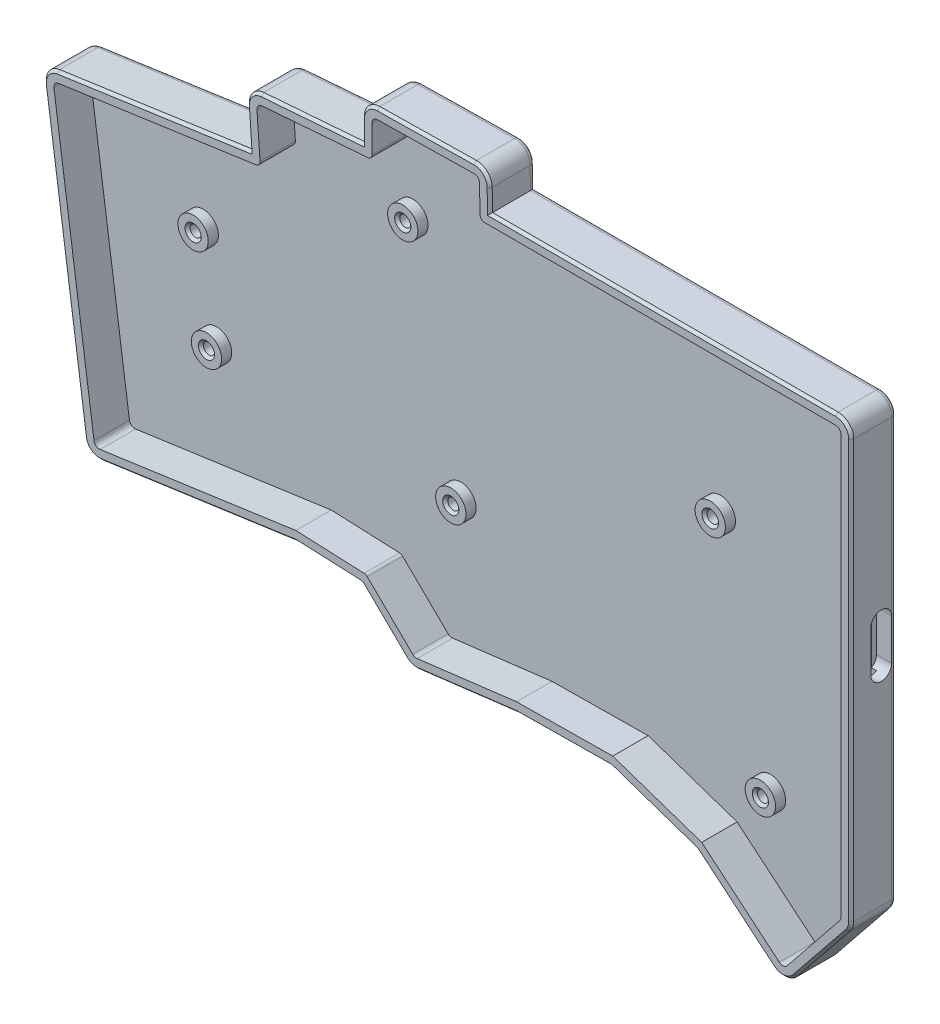
SolidWorks part; units mm, degrees
ref_plane "Front Plane" through (0, 0, 0) normal (0, 0, 1) x (1, 0, 0)
ref_plane "Top Plane" through (0, 0, 0) normal (0, 1, 0) x (1, 0, 0)
ref_plane "Right Plane" through (0, 0, 0) normal (1, 0, 0) x (0, 0, -1)
sketch "Sketch3" plane through (0, 0, 0) normal (0, 0, 1) x (1, 0, 0)
  line L0 (85.1833, 97.7805) -> (154.5968, 97.7805)
  line L1 (155.6718, 96.7055) -> (155.6718, 14.0578)
  line L2 (155.4344, 13.384) -> (144.9894, 0.4011)
  line L3 (143.4619, 0.2505) -> (128.1082, 13.0973)
  line L4 (128.1082, 13.0973) -> (143.4619, 0.2505)
  line L5 (128.1082, 13.0973) -> (110.5249, 19.0829)
  line L6 (110.5249, 19.0829) -> (91.5019, 18.8692)
  line L7 (91.5019, 18.8692) -> (71.8411, 16.4484)
  line L8 (70.9583, 16.7466) -> (61.9589, 25.5411)
  line L9 (70.9583, 16.7466) -> (61.9589, 25.5411)
  line L10 (61.3523, 25.8037) -> (47.8521, 26.3837)
  line L11 (47.8521, 26.3837) -> (9.158, 20.9127)
  line L12 (7.9428, 21.8276) -> (0.0098, 78.274)
  line L13 (0.9224, 79.4879) -> (39.9728, 85.0637)
  line L14 (40.7648, 86.0439) -> (40.1665, 94.5997)
  line L15 (41.1563, 95.7465) -> (62.0679, 97.3591)
  line L16 (62.9218, 98.2813) -> (62.9218, 103.7219)
  line L17 (63.979, 104.7967) -> (83.0927, 105.1138)
  line L18 (84.1855, 104.0536) -> (84.2584, 98.6929)
  line L19 (61.2805, 24.8059) -> (47.901, 25.3807)
  line L20 (47.901, 25.3807) -> (9.298, 19.9225)
  line L21 (6.9525, 21.6885) -> (-0.9804, 78.1349)
  line L22 (0.7811, 80.4778) -> (39.7624, 86.0438)
  line L23 (39.7624, 86.0438) -> (39.169, 94.5299)
  line L24 (41.0794, 96.7436) -> (61.9218, 98.3508)
  line L25 (61.9218, 98.3508) -> (61.9218, 103.7219)
  line L26 (63.9624, 105.7966) -> (83.0761, 106.1137)
  line L27 (85.1854, 104.0671) -> (85.2573, 98.7805)
  line L28 (85.2573, 98.7805) -> (154.5968, 98.7805)
  line L29 (156.6718, 96.7055) -> (156.6718, 14.0578)
  line L30 (156.2136, 12.7572) -> (145.7685, -0.2258)
  line L31 (142.8202, -0.5165) -> (127.6095, 12.2107)
  line L32 (127.6095, 12.2107) -> (110.3649, 18.081)
  line L33 (110.3649, 18.081) -> (91.5689, 17.8699)
  line L34 (91.5689, 17.8699) -> (71.9634, 15.4559)
  line L35 (70.2594, 16.0314) -> (61.2805, 24.8059)
  line L36 (60.8552, 23.8232) -> (47.95, 24.3777)
  line L37 (47.95, 24.3777) -> (9.438, 18.9324)
  line L38 (5.9622, 21.5493) -> (-1.9707, 77.9957)
  line L39 (0.6397, 81.4678) -> (38.6999, 86.9022)
  line L40 (38.6999, 86.9022) -> (38.1714, 94.4602)
  line L41 (41.0025, 97.7406) -> (60.9218, 99.2767)
  line L42 (60.9218, 99.2767) -> (60.9218, 103.7219)
  line L43 (63.9458, 106.7965) -> (83.0596, 107.1135)
  line L44 (86.1853, 104.0807) -> (86.2438, 99.7805)
  line L45 (86.2438, 99.7805) -> (154.5968, 99.7805)
  line L46 (157.6718, 96.7055) -> (157.6718, 14.0578)
  line L47 (156.9927, 12.1304) -> (146.5477, -0.8526)
  line L48 (142.1785, -1.2834) -> (127.1108, 11.3241)
  line L49 (127.1108, 11.3241) -> (110.2048, 17.0791)
  line L50 (110.2048, 17.0791) -> (91.6358, 16.8706)
  line L51 (91.6358, 16.8706) -> (72.0856, 14.4634)
  line L52 (69.5605, 15.3162) -> (60.8552, 23.8232)
  arc A0 (154.5968, 97.7805) -> (155.6718, 96.7055) centre (154.5968, 96.7055) cw
  arc A1 (155.6718, 14.0578) -> (155.4344, 13.384) centre (154.597, 14.0578) cw
  arc A2 (144.9894, 0.4011) -> (143.4619, 0.2505) centre (144.1518, 1.0749) cw
  arc A3 (71.8411, 16.4484) -> (70.9583, 16.7466) centre (71.7098, 17.5155) cw
  arc A4 (61.9589, 25.5411) -> (61.3523, 25.8037) centre (61.3124, 24.8796) ccw
  arc A5 (9.158, 20.9127) -> (7.9428, 21.8276) centre (9.0075, 21.9773) cw
  arc A6 (0.0098, 78.274) -> (0.9224, 79.4879) centre (1.0744, 78.4236) cw
  arc A7 (39.9728, 85.0637) -> (40.7648, 86.0439) centre (39.8421, 85.9794) ccw
  arc A8 (40.1665, 94.5997) -> (41.1563, 95.7465) centre (41.2389, 94.6747) cw
  arc A9 (62.0679, 97.3591) -> (62.9218, 98.2813) centre (61.9968, 98.2814) ccw
  arc A10 (62.9218, 103.7219) -> (63.979, 104.7967) centre (63.9968, 103.7219) cw
  arc A11 (83.0927, 105.1138) -> (84.1855, 104.0536) centre (83.1106, 104.0389) cw
  arc A12 (84.2584, 98.6929) -> (85.1833, 97.7805) centre (85.1833, 98.7055) ccw
  circle A13 centre (22.5341, 62.2507) radius 1.1001
  circle A14 centre (25.1783, 43.4356) radius 1.1001
  circle A15 centre (63.9968, 84.7054) radius 1.1001
  circle A16 centre (73.4968, 41.0054) radius 1.1001
  circle A17 centre (124.7968, 64.4055) radius 1.1454
  circle A18 centre (134.7093, 21.5464) radius 1.1001
  arc A19 (61.2805, 24.8059) -> (61.2805, 24.8059) centre (61.2805, 24.8059) ccw
  arc A20 (9.298, 19.9225) -> (6.9525, 21.6885) centre (9.0075, 21.9773) cw
  arc A21 (-0.9804, 78.1349) -> (0.7811, 80.4778) centre (1.0744, 78.4236) cw
  arc A22 (39.7624, 86.0438) -> (39.7624, 86.0438) centre (39.7624, 86.0438) ccw
  arc A23 (39.169, 94.5299) -> (41.0794, 96.7436) centre (41.2389, 94.6747) cw
  arc A24 (61.9218, 98.3508) -> (61.9218, 98.3508) centre (61.9218, 98.3508) ccw
  arc A25 (61.9218, 103.7219) -> (63.9624, 105.7966) centre (63.9968, 103.7219) cw
  arc A26 (83.0761, 106.1137) -> (85.1854, 104.0671) centre (83.1106, 104.0389) cw
  arc A27 (85.2573, 98.7805) -> (85.2573, 98.7805) centre (85.2573, 98.7805) ccw
  arc A28 (154.5968, 98.7805) -> (156.6718, 96.7055) centre (154.5968, 96.7055) cw
  arc A29 (156.6718, 14.0578) -> (156.2136, 12.7572) centre (154.597, 14.0578) cw
  arc A30 (145.7685, -0.2258) -> (142.8202, -0.5165) centre (144.1518, 1.0749) cw
  arc A31 (71.9634, 15.4559) -> (70.2594, 16.0314) centre (71.7098, 17.5155) cw
  arc A32 (9.438, 18.9324) -> (5.9622, 21.5493) centre (9.0075, 21.9773) cw
  arc A33 (-1.9707, 77.9957) -> (0.6397, 81.4678) centre (1.0744, 78.4236) cw
  arc A34 (38.6999, 86.9022) -> (38.6999, 86.9022) centre (38.6999, 86.9022) ccw
  arc A35 (38.1714, 94.4602) -> (41.0025, 97.7406) centre (41.2389, 94.6747) cw
  arc A36 (60.9218, 99.2767) -> (60.9218, 99.2767) centre (60.9218, 99.2767) ccw
  arc A37 (60.9218, 103.7219) -> (63.9458, 106.7965) centre (63.9968, 103.7219) cw
  arc A38 (83.0596, 107.1135) -> (86.1853, 104.0807) centre (83.1106, 104.0389) cw
  arc A39 (86.2438, 99.7805) -> (86.2438, 99.7805) centre (86.2438, 99.7805) ccw
  arc A40 (154.5968, 99.7805) -> (157.6718, 96.7055) centre (154.5968, 96.7055) cw
  arc A41 (157.6718, 14.0578) -> (156.9927, 12.1304) centre (154.597, 14.0578) cw
  arc A42 (146.5477, -0.8526) -> (142.1785, -1.2834) centre (144.1518, 1.0749) cw
  arc A43 (72.0856, 14.4634) -> (69.5605, 15.3162) centre (71.7098, 17.5155) cw
  arc A44 (60.8552, 23.8232) -> (60.8552, 23.8232) centre (60.8552, 23.8232) ccw
  dimension "D1" = 1
  dimension "D2" = 1
extrude "Boss-Extrude1" add sketch "Sketch3" along normal blind 2 contours A43 L51 L50 L49 L48 A42 L47 A41 L46 A40 L45 L44 A38 L43 A37 L42 L41 A35 L40 L39 A33 L38 A32 L37 L36 L52 L34 A31 L35 L19 L20 A20 L21 A21 L22 L23 A23 L24 L25 A25 L26 A26 L27 L28 A28 L29 A29 L30 A30 L31 | A31 L34 L33 L32 L31 A30 L30 A29 L29 A28 L28 L27 A26 L26 A25 L25 L24 A23 L23 L22 A21 L21 A20 L20 L19 L35 L18 A12 L0 A0 L1 A1 L2 A2 L3 L5 L6 L7 A3 L8 A4 L10 L11 A5 L12 A6 L13 A7 L14 A8 | A12 L18 A11 L17 A10 L16 A9 L15 A8 L14 A7 L13 A6 L12 A5 L11 L10 A4 L8 A3 L7 L6 L5 L3 A2 L2 A1 L1 A0 L0 A18 A17 A16 A15 A14 A13 | A13 | A14 | A15 | A16 | A17 | A18 region at (85.6931, 56.8689, 0) region at (54.5989, 25.2837, 0) region at (54.4109, 24.2937, 0) region at (22.5341, 62.2507, 0) region at (25.1783, 43.4356, 0) region at (63.9968, 84.7054, 0) region at (73.4968, 41.0054, 0) region at (124.7968, 64.4055, 0) region at (134.7093, 21.5464, 0)
sketch "Sketch4" plane through (0, 0, 0) normal (0, 0, 1) x (1, 0, 0)
  line L0 (85.1833, 97.7805) -> (154.5968, 97.7805)
  line L1 (155.6718, 96.7055) -> (155.6718, 14.0578)
  line L2 (155.4344, 13.384) -> (144.9894, 0.4011)
  line L3 (143.4619, 0.2505) -> (128.1082, 13.0973)
  line L4 (128.1082, 13.0973) -> (143.4619, 0.2505)
  line L5 (128.1082, 13.0973) -> (110.5249, 19.0829)
  line L6 (110.5249, 19.0829) -> (91.5019, 18.8692)
  line L7 (91.5019, 18.8692) -> (71.8411, 16.4484)
  line L8 (70.9583, 16.7466) -> (61.9589, 25.5411)
  line L9 (70.9583, 16.7466) -> (61.9589, 25.5411)
  line L10 (61.3523, 25.8037) -> (47.8521, 26.3837)
  line L11 (47.8521, 26.3837) -> (9.158, 20.9127)
  line L12 (7.9428, 21.8276) -> (0.0098, 78.274)
  line L13 (0.9224, 79.4879) -> (39.9728, 85.0637)
  line L14 (40.7648, 86.0439) -> (40.1665, 94.5997)
  line L15 (41.1563, 95.7465) -> (62.0679, 97.3591)
  line L16 (62.9218, 98.2813) -> (62.9218, 103.7219)
  line L17 (63.979, 104.7967) -> (83.0927, 105.1138)
  line L18 (84.1855, 104.0536) -> (84.2584, 98.6929)
  line L19 (61.2805, 24.8059) -> (47.901, 25.3807)
  line L20 (47.901, 25.3807) -> (9.298, 19.9225)
  line L21 (6.9525, 21.6885) -> (-0.9804, 78.1349)
  line L22 (0.7811, 80.4778) -> (39.7624, 86.0438)
  line L23 (39.7624, 86.0438) -> (39.169, 94.5299)
  line L24 (41.0794, 96.7436) -> (61.9218, 98.3508)
  line L25 (61.9218, 98.3508) -> (61.9218, 103.7219)
  line L26 (63.9624, 105.7966) -> (83.0761, 106.1137)
  line L27 (85.1854, 104.0671) -> (85.2573, 98.7805)
  line L28 (85.2573, 98.7805) -> (154.5968, 98.7805)
  line L29 (156.6718, 96.7055) -> (156.6718, 14.0578)
  line L30 (156.2136, 12.7572) -> (145.7685, -0.2258)
  line L31 (142.8202, -0.5165) -> (127.6095, 12.2107)
  line L32 (127.6095, 12.2107) -> (110.3649, 18.081)
  line L33 (110.3649, 18.081) -> (91.5689, 17.8699)
  line L34 (91.5689, 17.8699) -> (71.9634, 15.4559)
  line L35 (70.2594, 16.0314) -> (61.2805, 24.8059)
  line L36 (60.8552, 23.8232) -> (47.95, 24.3777)
  line L37 (47.95, 24.3777) -> (9.438, 18.9324)
  line L38 (5.9622, 21.5493) -> (-1.9707, 77.9957)
  line L39 (0.6397, 81.4678) -> (38.6999, 86.9022)
  line L40 (38.6999, 86.9022) -> (38.1714, 94.4602)
  line L41 (41.0025, 97.7406) -> (60.9218, 99.2767)
  line L42 (60.9218, 99.2767) -> (60.9218, 103.7219)
  line L43 (63.9458, 106.7965) -> (83.0596, 107.1135)
  line L44 (86.1853, 104.0807) -> (86.2438, 99.7805)
  line L45 (86.2438, 99.7805) -> (154.5968, 99.7805)
  line L46 (157.6718, 96.7055) -> (157.6718, 14.0578)
  line L47 (156.9927, 12.1304) -> (146.5477, -0.8526)
  line L48 (142.1785, -1.2834) -> (127.1108, 11.3241)
  line L49 (127.1108, 11.3241) -> (110.2048, 17.0791)
  line L50 (110.2048, 17.0791) -> (91.6358, 16.8706)
  line L51 (91.6358, 16.8706) -> (72.0856, 14.4634)
  line L52 (69.5605, 15.3162) -> (60.8552, 23.8232)
  arc A0 (154.5968, 97.7805) -> (155.6718, 96.7055) centre (154.5968, 96.7055) cw
  arc A1 (155.6718, 14.0578) -> (155.4344, 13.384) centre (154.597, 14.0578) cw
  arc A2 (144.9894, 0.4011) -> (143.4619, 0.2505) centre (144.1518, 1.0749) cw
  arc A3 (71.8411, 16.4484) -> (70.9583, 16.7466) centre (71.7098, 17.5155) cw
  arc A4 (61.9589, 25.5411) -> (61.3523, 25.8037) centre (61.3124, 24.8796) ccw
  arc A5 (9.158, 20.9127) -> (7.9428, 21.8276) centre (9.0075, 21.9773) cw
  arc A6 (0.0098, 78.274) -> (0.9224, 79.4879) centre (1.0744, 78.4236) cw
  arc A7 (39.9728, 85.0637) -> (40.7648, 86.0439) centre (39.8421, 85.9794) ccw
  arc A8 (40.1665, 94.5997) -> (41.1563, 95.7465) centre (41.2389, 94.6747) cw
  arc A9 (62.0679, 97.3591) -> (62.9218, 98.2813) centre (61.9968, 98.2814) ccw
  arc A10 (62.9218, 103.7219) -> (63.979, 104.7967) centre (63.9968, 103.7219) cw
  arc A11 (83.0927, 105.1138) -> (84.1855, 104.0536) centre (83.1106, 104.0389) cw
  arc A12 (84.2584, 98.6929) -> (85.1833, 97.7805) centre (85.1833, 98.7055) ccw
  circle A13 centre (22.5341, 62.2507) radius 1.1001
  circle A14 centre (25.1783, 43.4356) radius 1.1001
  circle A15 centre (63.9968, 84.7054) radius 1.1001
  circle A16 centre (73.4968, 41.0054) radius 1.1001
  circle A17 centre (124.7968, 64.4055) radius 1.1454
  circle A18 centre (134.7093, 21.5464) radius 1.1001
  arc A19 (61.2805, 24.8059) -> (61.2805, 24.8059) centre (61.2805, 24.8059) ccw
  arc A20 (9.298, 19.9225) -> (6.9525, 21.6885) centre (9.0075, 21.9773) cw
  arc A21 (-0.9804, 78.1349) -> (0.7811, 80.4778) centre (1.0744, 78.4236) cw
  arc A22 (39.7624, 86.0438) -> (39.7624, 86.0438) centre (39.7624, 86.0438) ccw
  arc A23 (39.169, 94.5299) -> (41.0794, 96.7436) centre (41.2389, 94.6747) cw
  arc A24 (61.9218, 98.3508) -> (61.9218, 98.3508) centre (61.9218, 98.3508) ccw
  arc A25 (61.9218, 103.7219) -> (63.9624, 105.7966) centre (63.9968, 103.7219) cw
  arc A26 (83.0761, 106.1137) -> (85.1854, 104.0671) centre (83.1106, 104.0389) cw
  arc A27 (85.2573, 98.7805) -> (85.2573, 98.7805) centre (85.2573, 98.7805) ccw
  arc A28 (154.5968, 98.7805) -> (156.6718, 96.7055) centre (154.5968, 96.7055) cw
  arc A29 (156.6718, 14.0578) -> (156.2136, 12.7572) centre (154.597, 14.0578) cw
  arc A30 (145.7685, -0.2258) -> (142.8202, -0.5165) centre (144.1518, 1.0749) cw
  arc A31 (71.9634, 15.4559) -> (70.2594, 16.0314) centre (71.7098, 17.5155) cw
  arc A32 (9.438, 18.9324) -> (5.9622, 21.5493) centre (9.0075, 21.9773) cw
  arc A33 (-1.9707, 77.9957) -> (0.6397, 81.4678) centre (1.0744, 78.4236) cw
  arc A34 (38.6999, 86.9022) -> (38.6999, 86.9022) centre (38.6999, 86.9022) ccw
  arc A35 (38.1714, 94.4602) -> (41.0025, 97.7406) centre (41.2389, 94.6747) cw
  arc A36 (60.9218, 99.2767) -> (60.9218, 99.2767) centre (60.9218, 99.2767) ccw
  arc A37 (60.9218, 103.7219) -> (63.9458, 106.7965) centre (63.9968, 103.7219) cw
  arc A38 (83.0596, 107.1135) -> (86.1853, 104.0807) centre (83.1106, 104.0389) cw
  arc A39 (86.2438, 99.7805) -> (86.2438, 99.7805) centre (86.2438, 99.7805) ccw
  arc A40 (154.5968, 99.7805) -> (157.6718, 96.7055) centre (154.5968, 96.7055) cw
  arc A41 (157.6718, 14.0578) -> (156.9927, 12.1304) centre (154.597, 14.0578) cw
  arc A42 (146.5477, -0.8526) -> (142.1785, -1.2834) centre (144.1518, 1.0749) cw
  arc A43 (72.0856, 14.4634) -> (69.5605, 15.3162) centre (71.7098, 17.5155) cw
  arc A44 (60.8552, 23.8232) -> (60.8552, 23.8232) centre (60.8552, 23.8232) ccw
  dimension "D1" = 1
  dimension "D2" = 1
extrude "Boss-Extrude2" add sketch "Sketch4" along normal blind 9 contours A43 L51 L50 L49 L48 A42 L47 A41 L46 A40 L45 L44 A38 L43 A37 L42 L41 A35 L40 L39 A33 L38 A32 L37 L36 L52 L34 A31 L35 L19 L20 A20 L21 A21 L22 L23 A23 L24 L25 A25 L26 A26 L27 L28 A28 L29 A29 L30 A30 L31 | A31 L34 L33 L32 L31 A30 L30 A29 L29 A28 L28 L27 A26 L26 A25 L25 L24 A23 L23 L22 A21 L21 A20 L20 L19 L35 L18 A12 L0 A0 L1 A1 L2 A2 L3 L5 L6 L7 A3 L8 A4 L10 L11 A5 L12 A6 L13 A7 L14 A8 region at (54.5989, 25.2837, 0) region at (54.4109, 24.2937, 0)
sketch "Sketch7" plane through (0, 0, 0) normal (0, 0, 1) x (1, 0, 0)
  circle A0 centre (25.1783, 43.4356) radius 3
  circle A1 centre (22.5341, 62.2507) radius 3
  circle A2 centre (63.9968, 84.7054) radius 3
  circle A3 centre (73.4968, 41.0054) radius 3
  circle A4 centre (124.7968, 64.4055) radius 3
  circle A5 centre (134.7093, 21.5464) radius 3
  circle A13 centre (22.5341, 62.2507) radius 1.1001
  circle A14 centre (25.1783, 43.4356) radius 1.1001
  circle A15 centre (63.9968, 84.7054) radius 1.1001
  circle A16 centre (73.4968, 41.0054) radius 1.1001
  circle A17 centre (124.7968, 64.4055) radius 1.1454
  circle A18 centre (134.7093, 21.5464) radius 1.1001
  dimension "D1" = 6
  dimension "D2" = 6
  dimension "D3" = 6
  dimension "D4" = 6
  dimension "D5" = 6
  dimension "D6" = 6
extrude "Boss-Extrude3" add sketch "Sketch7" along normal blind 4
sketch "Sketch8" plane through (157.6718, 0, 0) normal (1, 0, 0) x (0, 0, -1)
  line L0 (0, 96.7055) -> (0, 14.0578) construction
  line L5 (-3.0616, 62.6695) -> (-3.0616, 54.5415) construction
  line L6 (-1, 62.6695) -> (-1, 54.5415)
  line L7 (-5.1232, 62.6695) -> (-5.1232, 54.5415)
  line L8 (-9, 96.7055) -> (0, 96.7055) construction
  arc A0 (-1, 62.6695) -> (-5.1232, 62.6695) centre (-3.0616, 62.6695) ccw
  arc A1 (-5.1232, 54.5415) -> (-1, 54.5415) centre (-3.0616, 54.5415) ccw
  point P8 (-3.0616, 58.6055)
  dimension "D1" = 8.128
  dimension "D2" = 1
  dimension "D3" = 34.036
extrude "Cut-Extrude1" cut sketch "Sketch8" against normal blind 3
fillet "Fillet2" radius 1 26 edges at (81.8607, 15.667, 0) (100.9203, 16.9749, 0) (118.6578, 14.2016, 0) (134.6446, 5.0203, 0) (144.4535, -1.9852, 0) (151.7702, 5.6389, 0) (157.4971, 13.036, 0) (157.6718, 55.3816, 0) (156.7712, 98.8798, 0) (120.4203, 99.7805, 0) (86.2145, 101.9306, 0) (85.2519, 106.2459, 0) (73.5027, 106.955, 0) (61.8045, 105.8781, 0) (60.9218, 101.4993, 0) (50.9622, 98.5086, 0) (38.911, 96.6838, 0) (38.4356, 90.6812, 0) (54.4026, 24.1004, 0) (65.2079, 19.5697, 0) (70.7258, 14.602, 0) (19.6698, 84.185, 0) (-1.3835, 80.2715, 0) (1.9958, 49.7725, 0) (7.1578, 19.5206, 0) (28.694, 21.655, 0)
chamfer "Chamfer1" distance 0.5 angle 45 26 edges at (65.2079, 19.5697, 9) (54.4026, 24.1004, 9) (70.7258, 14.602, 9) (81.8607, 15.667, 9) (100.9203, 16.9749, 9) (118.6578, 14.2016, 9) (134.6446, 5.0203, 9) (144.4535, -1.9852, 9) (151.7702, 5.6389, 9) (157.4971, 13.036, 9) (157.6718, 55.3816, 9) (156.7712, 98.8798, 9) (120.4203, 99.7805, 9) (86.2145, 101.9306, 9) (85.2519, 106.2459, 9) (73.5027, 106.955, 9) (61.8045, 105.8781, 9) (60.9218, 101.4993, 9) (50.9622, 98.5086, 9) (38.911, 96.6838, 9) (38.4356, 90.6812, 9) (19.6698, 84.185, 9) (-1.3835, 80.2715, 9) (1.9958, 49.7725, 9) (7.1578, 19.5206, 9) (28.694, 21.655, 9)
chamfer "Chamfer2" distance 0.5 angle 45 6 edges at (26.2784, 43.4356, 4) (74.5969, 41.0054, 4) (135.8094, 21.5464, 4) (125.9422, 64.4055, 4) (65.0969, 84.7054, 4) (23.6341, 62.2507, 4)
